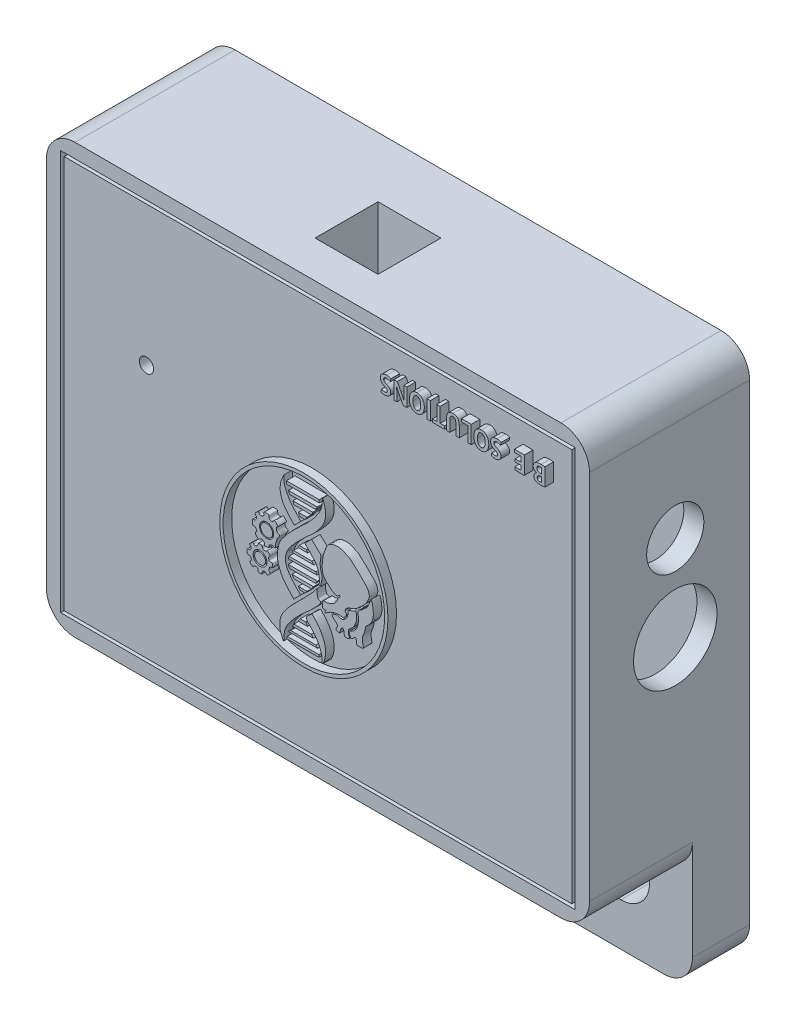
SolidWorks part; units mm, degrees
note: The reader was unsure of these and kept them because the rebuilt part matched: shared geometry of "Sketch12<3>".
ref_plane "Front Plane" through (0, 0, 0) normal (0, 0, 1) x (1, 0, 0)
ref_plane "Top Plane" through (0, 0, 0) normal (0, 1, 0) x (1, 0, 0)
ref_plane "Right Plane" through (0, 0, 0) normal (1, 0, 0) x (0, 0, -1)
sketch "Sketch2" plane through (0, 0, 0) normal (0, 0, 1) x (1, 0, 0)
  line L1 (0, 0) -> (190, 0)
  line L2 (0, 0) -> (0, 150)
  line L3 (0, 150) -> (190, 150)
  line L4 (190, 0) -> (190, 150)
  line L5 (7, 7) -> (183, 7)
  line L6 (7, 7) -> (7, 143)
  line L7 (7, 143) -> (183, 143)
  line L8 (183, 7) -> (183, 143)
  dimension "D1" = 190
  dimension "D2" = 150
  dimension "D3" = 7
  dimension "D4" = 7
  dimension "D5" = 7
  dimension "D6" = 7
extrude "Boss-Extrude1" add sketch "Sketch2" against normal blind 50
sketch "Sketch3" plane through (0, 0, 0) normal (0, 0, 1) x (1, 0, 0)
  line L1 (185, 145) -> (5, 145)
  line L2 (185, 145) -> (185, 5)
  line L3 (185, 5) -> (5, 5)
  line L4 (5, 145) -> (5, 5)
  line L5 (190, 150) -> (0, 150)
  line L6 (190, 150) -> (190, 0)
  line L7 (190, 0) -> (0, 0)
  line L8 (0, 150) -> (0, 0)
  line M9 (183, 7) -> (7, 7)
  line M10 (7, 7) -> (7, 143)
  line M11 (7, 143) -> (183, 143)
  line M12 (183, 143) -> (183, 7)
  dimension "D1" = 5
  dimension "D2" = 5
  dimension "D3" = 5
  dimension "D4" = 5
extrude "Cut-Extrude1" cut sketch "Sketch3" against normal blind 6 contours L1 L4 L3 L2 M12 M9 M10 M11
sketch "Sketch5" plane through (0, 0, -6) normal (0, 0, 1) x (1, 0, 0)
  line L0 (185, 5) -> (5, 5) construction
  line L1 (183.8, 143.8) -> (6.2, 143.8)
  line L2 (183.8, 143.8) -> (183.8, 6.2)
  line L3 (183.8, 6.2) -> (6.2, 6.2)
  line L4 (6.2, 143.8) -> (6.2, 6.2)
  line L5 (5, 145) -> (5, 5) construction
  line L6 (185, 145) -> (5, 145) construction
  line L7 (185, 145) -> (185, 5) construction
  dimension "D1" = 1.2
  dimension "D2" = 1.2
  dimension "D3" = 1.2
  dimension "D4" = 1.2
extrude "Boss-Extrude2" add sketch "Sketch5" along normal up to surface (6 mm away) separate body up to face at (95, 75, 0)
sketch "Sketch6" plane through (0, 0, -50) normal (0, 0, -1) x (-1, 0, 0)
  line L1 (0, 150) -> (-190, 150)
  line L2 (0, 150) -> (0, 0)
  line L3 (0, 0) -> (-190, 0)
  line L4 (-190, 150) -> (-190, 0)
extrude "Boss-Extrude3" add sketch "Sketch6" along normal blind 6
sketch "Sketch8" plane through (0, 0, -56) normal (0, 0, -1) x (-1, 0, 0)
  line L2 (-190, 0) -> (-190, -35)
  line L3 (-190, -35) -> (0, -35)
  line L4 (0, 0) -> (0, -35)
  line L7 (0, 0) -> (-190, 0)
  line L9 (-175, 0) -> (-175, -20)
  line L10 (-175, -20) -> (-15, -20)
  line L11 (-15, 0) -> (-15, -20)
  point P0 (-90, 0)
  point P7 (-135, 0)
  line M15 (-190, 0) -> (0, 0)
  dimension "D1" = 190
  dimension "D2" = 15
  dimension "D3" = 15
  dimension "D4" = 15
  dimension "D5" = 0
  dimension "D6" = 20
extrude "Boss-Extrude5" add sketch "Sketch8" against normal blind 20 contours L11 L10 L9 L2 L3 L4 M15
fillet "Fillet1" radius 10 2 edges at (0, 150, -28) (0, 0, -18)
fillet "Fillet2" radius 10 2 edges at (190, 150, -28) (190, 0, -18)
fillet "Fillet3" radius 10 4 edges at (175, -20, -46) (15, -20, -46) (0, -35, -46) (190, -35, -46)
sketch "Sketch12" plane through (0, 143, 0) normal (0, -1, 0) x (1, 0, 0)
  line L0 (183, -50) -> (183, -6) construction
  line L1 (103, -35) -> (81, -35)
  line L2 (103, -35) -> (103, -13)
  line L3 (103, -13) -> (81, -13)
  line L4 (81, -35) -> (81, -13)
  line L5 (103, -35) -> (81, -13) construction
  line L6 (103, -13) -> (81, -35) construction
  line L7 (183, -50) -> (7, -50) construction
  line L9 (107, -9) -> (77, -9)
  line L10 (107, -9) -> (107, -39)
  line L11 (107, -39) -> (77, -39)
  line L12 (77, -9) -> (77, -39)
  line L13 (107, -9) -> (77, -39) construction
  line L14 (107, -39) -> (77, -9) construction
  point P0 (92, -24)
  point P9 (92, -24)
  dimension "D1" = 22
  dimension "D2" = 22
  dimension "D3" = 80
  dimension "D4" = 15
  dimension "D5" = 4
  dimension "D6" = 4
extrude "Cut-Extrude3" cut sketch "Sketch12" against normal blind 27 contours L2 L1 L4 L3
extrude "Boss-Extrude7" add sketch "Sketch12<3>" along normal blind 25 contours L10 L11 L12 L9
sketch "Sketch12<3>" plane through (0, 143, 0) normal (0, -1, 0) x (1, 0, 0) same geometry as "Sketch12"
sketch "Sketch13" plane through (0, 0, -9) normal (0, 0, 1) x (1, 0, 0)
  line L1 (107, 118) -> (77, 118)
  line L2 (107, 118) -> (107, 115)
  line L3 (107, 115) -> (77, 115)
  line L4 (77, 118) -> (77, 115)
  dimension "D1" = 0
  dimension "D2" = 3
extrude "Boss-Extrude8" add sketch "Sketch13" against normal blind 24
sketch "Sketch14" plane through (190, 0, 0) normal (1, 0, 0) x (0, 0, -1)
  line L0 (56, 75) -> (0, 75) construction
  line L1 (56, 140) -> (56, -25) construction
  line L2 (0, 10) -> (0, 140) construction
  circle A0 centre (30, 75) radius 14.6
  dimension "D2" = 29.2
  dimension "D3" = 30
  dimension "D1" = 70
extrude "Cut-Extrude4" cut sketch "Sketch14" against normal blind 24
sketch "Sketch15" plane through (0, 0, 0) normal (0, 0, 1) x (1, 0, 0)
  line L0 (178, 136.8993) -> (98, 136.8993) construction
  line L2 (185, 145) -> (185, 5) construction
  text T0 "B.E. SOLUTIONS\r\n" font "Adobe Gothic Std B" height in points 20
  dimension "D1" = 7
  dimension "D2" = 80
extrude "Boss-Extrude10" add sketch "Sketch15" along normal blind 3
sketch "Sketch16" plane through (0, 0, 0) normal (0, 0, 1) x (1, 0, 0)
  line L0 (9.3333, -352) -> (-673.3333, -352) construction
  line L1 (92.6849, 54.4735) -> (90.2161, 52.2125)
  line L2 (91.9334, 55.2949) -> (89.5639, 52.9254)
  line L3 (95.7514, 74.0964) -> (93.3973, 71.6991)
  line L4 (93.3973, 71.6991) -> (93.5085, 71.5841)
  line L5 (98.3461, 61.5576) -> (99.1025, 61.5576)
  line L6 (92.0206, 77.667) -> (89.6937, 75.3401)
  line L7 (98.3461, 39.6401) -> (98.3461, 40.4546)
  line L8 (98.3461, 40.4546) -> (87.2348, 40.4546)
  line L9 (87.2348, 40.4546) -> (87.2348, 39.6401)
  line L10 (87.2348, 39.6401) -> (98.3461, 39.6401)
  line L11 (97.8898, 42.126) -> (97.2739, 42.8467)
  line L12 (97.2739, 42.8467) -> (88.4308, 42.8467)
  line L13 (88.4308, 42.8467) -> (87.5876, 42.126)
  line L14 (87.5876, 42.126) -> (97.8898, 42.126)
  line L15 (96.4473, 44.4542) -> (95.7514, 45.3202)
  line L16 (95.7514, 45.3202) -> (89.5639, 45.3202)
  line L17 (89.5639, 45.3202) -> (89.0336, 44.4542)
  line L18 (89.0336, 44.4542) -> (96.4473, 44.4542)
  line L19 (94.3242, 46.9907) -> (91.0841, 46.9907)
  line L20 (91.0841, 46.9907) -> (91.7933, 48.0423)
  line L21 (91.7933, 48.0423) -> (93.6841, 48.0423)
  line L22 (93.6841, 48.0423) -> (94.3242, 46.9907)
  line L23 (94.1769, 57.5409) -> (93.5085, 56.6946)
  line L24 (93.5085, 56.6946) -> (91.7933, 56.6946)
  line L25 (91.7933, 56.6946) -> (91.1131, 57.5409)
  line L26 (91.1131, 57.5409) -> (94.1769, 57.5409)
  line L27 (96.3957, 60.0816) -> (95.719, 59.0603)
  line L28 (95.719, 59.0603) -> (89.6239, 59.0603)
  line L29 (89.6239, 59.0603) -> (88.9199, 60.0816)
  line L30 (88.9199, 60.0816) -> (96.3957, 60.0816)
  line L31 (97.758, 62.4384) -> (97.1874, 61.4488)
  line L32 (97.1874, 61.4488) -> (88.0735, 61.4488)
  line L33 (88.0735, 61.4488) -> (87.5876, 62.4384)
  line L34 (87.5876, 62.4384) -> (97.758, 62.4384)
  line L35 (97.6067, 64.1731) -> (97.2378, 65.0258)
  line L36 (97.2378, 65.0258) -> (87.8826, 65.0258)
  line L37 (87.8826, 65.0258) -> (87.5876, 64.1731)
  line L38 (87.5876, 64.1731) -> (97.6067, 64.1731)
  line L39 (96.5562, 66.7164) -> (95.8785, 67.557)
  line L40 (95.8785, 67.557) -> (89.4203, 67.557)
  line L41 (89.4203, 67.557) -> (88.8793, 66.7164)
  line L42 (88.8793, 66.7164) -> (96.5562, 66.7164)
  line L43 (94.3614, 69.2592) -> (93.9954, 70.0943)
  line L44 (93.9954, 70.0943) -> (91.4569, 70.0943)
  line L45 (91.4569, 70.0943) -> (90.9302, 69.2758)
  line L46 (90.9302, 69.2758) -> (94.3614, 69.2592)
  line L47 (94.1769, 79.9875) -> (91.1131, 79.9875)
  line L48 (91.1131, 79.9875) -> (91.7933, 78.9617)
  line L49 (91.7933, 78.9617) -> (93.5085, 78.9617)
  line L50 (93.5085, 78.9617) -> (94.1769, 79.9875)
  line L51 (96.1948, 82.5266) -> (95.719, 81.5066)
  line L52 (95.719, 81.5066) -> (89.5639, 81.5066)
  line L53 (89.5639, 81.5066) -> (89.2463, 82.5266)
  line L54 (89.2463, 82.5266) -> (96.1948, 82.5266)
  line L55 (97.7527, 84.8946) -> (97.2378, 83.864)
  line L56 (97.2378, 83.864) -> (88.0735, 83.864)
  line L57 (88.0735, 83.864) -> (87.6796, 84.8946)
  line L58 (87.6796, 84.8946) -> (97.7527, 84.8946)
  line L59 (98.4337, 86.4686) -> (98.4337, 87.4496)
  line L60 (98.4337, 87.4496) -> (86.9516, 87.4496)
  line L61 (86.9516, 87.4496) -> (86.9516, 86.4686)
  line L62 (86.9516, 86.4686) -> (98.4337, 86.4686)
  circle A0 centre (93.074, 63.4201) radius 28.2643
  circle A1 centre (93.074, 63.4201) radius 29.417
  circle A2 centre (77.734, 59.328) radius 1.9037
  circle A3 centre (77.734, 59.328) radius 2.4063
  circle A4 centre (80.0465, 68.9893) radius 2.0884
  circle A5 centre (80.0465, 68.9893) radius 2.4688
  spline S0 degree 3 poles (100.0814, 39.1112) (99.4401, 37.9116) (99.4967, 39.8659) (99.3244, 40.7939) (98.8886, 42.3372) (98.2061, 43.7532) (97.388, 45.1029) (96.3568, 46.4662) (95.2159, 47.5835) (94.193, 48.5893) (93.7591, 49.5701) (94.2613, 50.133) (94.692, 50.4928) (95.1699, 50.9134) (95.4839, 51.2743) (96.0754, 51.5285) (96.5483, 50.8523) (97.2086, 50.221) (98.1892, 49.1071) (99.3075, 47.3884) (100.2855, 45.3363) (100.6265, 43.4327) (100.6737, 41.7822) (100.4361, 40.1463) (100.0814, 39.1112) (99.4401, 37.9116) (99.4967, 39.8659) knots -0.123491 -0.065666 -0.01284 0 0.039755 0.085413 0.127589 0.187562 0.242991 0.281899 0.356235 0.397229 0.429388 0.443556 0.466975 0.485881 0.505841 0.514143 0.545002 0.567755 0.609797 0.687896 0.770733 0.831317 0.876509 0.934334 0.98716 1 1.039755 1.085413 1.127589 only from (99.6247, 38.3159) to (99.6247, 38.3159)
  spline S1 degree 3 poles (85.4196, 39.6043) (86.1158, 37.7797) (86.0483, 39.9395) (86.2069, 41.1299) (86.6342, 42.772) (87.4046, 44.1741) (88.1754, 45.184) (88.979, 46.2387) (89.8787, 47.271) (91.165, 48.6525) (92.5075, 49.8902) (93.7687, 51.1266) (94.9955, 52.0558) (96.1288, 53.2053) (97.2902, 54.3109) (98.1886, 55.2936) (98.7359, 56.0378) (98.9055, 56.4995) (99.06, 56.9828) (98.5372, 57.0233) (98.078, 57.1348) (97.8136, 57.9254) (97.5879, 58.6477) (97.8074, 60.4824) (96.5577, 58.5767) (95.6222, 57.7056) (94.4154, 56.2661) (93.2173, 55.2059) (92.278, 54.0644) (91.0849, 53.0399) (90.0988, 51.9677) (88.9174, 50.8452) (87.7961, 49.6019) (86.6602, 48.1509) (85.5886, 46.7046) (85.014, 45.2448) (84.6196, 43.8471) (84.6275, 42.2966) (84.7957, 40.6496) (85.4196, 39.6043) (86.1158, 37.7797) (86.0483, 39.9395) knots -0.080081 -0.042595 -0.023219 0 0.020603 0.051768 0.084205 0.109791 0.141798 0.154959 0.18403 0.218361 0.260543 0.286188 0.317123 0.346418 0.376481 0.406547 0.421867 0.426234 0.435696 0.441637 0.450667 0.461443 0.482878 0.503861 0.523137 0.564277 0.596446 0.62275 0.654702 0.678549 0.710636 0.736113 0.769738 0.804156 0.839403 0.869741 0.891531 0.919919 0.957405 0.976781 1 1.020603 1.051768 1.084205 only from (85.998, 38.4137) to (85.998, 38.4137)
  spline S2 degree 3 poles (91.9334, 55.2949) (91.6406, 55.7586) (90.8902, 56.2469) (90.1919, 57.1207) (89.5579, 57.7611) (88.9438, 58.4408) (88.1526, 59.5625) (87.2316, 60.8609) (86.6476, 62.4983) (86.6273, 63.6811) (86.681, 64.7395) (86.8736, 65.6546) (87.4034, 66.7025) (88.0432, 67.8338) (89.2054, 69.2129) (90.4493, 70.5281) (91.6612, 71.6992) (92.7933, 72.8339) (93.8531, 73.9473) (95.2381, 75.0443) (96.4697, 76.1726) (97.7828, 77.6849) (99.1803, 79.4117) (100.2385, 81.2744) (100.6837, 83.2907) (100.6602, 85.1602) (100.3438, 86.5899) (99.5155, 89.3865) (99.5374, 86.8664) (99.2904, 85.3297) (98.4754, 83.5166) (97.313, 81.956) (96.4612, 80.6548) (95.3391, 79.618) (94.2884, 78.3301) (93.0377, 77.1702) (91.3991, 75.6092) (90.0592, 74.3939) (88.7326, 73.0228) (87.2054, 71.4292) (85.7379, 69.6213) (84.5028, 67.6851) (84.1105, 66.2454) (83.8768, 64.7084) (83.7797, 63.2592) (83.961, 61.4315) (84.5677, 59.5103) (85.656, 57.2186) (87.4999, 55.2161) (88.7313, 53.6243) (89.5639, 52.9254) knots 0 0 0 0 0.019361 0.031665 0.040167 0.05189 0.064656 0.089683 0.10912 0.126258 0.131963 0.147406 0.15948 0.174211 0.194215 0.224289 0.239579 0.255009 0.282159 0.294895 0.318724 0.342314 0.367054 0.39905 0.418045 0.441879 0.462155 0.483751 0.500653 0.518786 0.549837 0.567176 0.589792 0.605427 0.622108 0.649675 0.66685 0.70381 0.714899 0.735691 0.783444 0.798798 0.818064 0.836631 0.854984 0.870281 0.902638 0.927178 0.961174 1 1 1 1
  spline S3 degree 3 poles (98.3461, 61.5576) (98.5654, 62.3743) (98.5292, 63.7294) (98.1478, 65.6942) (97.5798, 67.4088) (96.2837, 68.717) (95.1023, 70.2157) (94.0343, 71.0212) (93.5085, 71.5841) knots 0 0 0 0 0.214269 0.339584 0.513108 0.662845 0.803202 1 1 1 1
  spline S4 degree 3 poles (95.7514, 74.0964) (96.2546, 73.5392) (97.1547, 72.8305) (98.2042, 71.7149) (99.1431, 70.959) (98.8402, 69.5975) (98.7485, 68.5373) (98.8158, 67.3781) (98.9095, 66.4977) (99.2365, 65.5048) (99.5616, 64.5902) (99.3576, 63.2533) (98.9896, 62.3616) (99.1025, 61.5576) knots 0 0 0 0 0.162649 0.23774 0.341133 0.380335 0.523449 0.573125 0.628859 0.712466 0.798393 0.829985 1 1 1 1
  spline S5 degree 3 poles (92.0206, 77.667) (91.4526, 78.3482) (90.3586, 79.4884) (88.9003, 80.9272) (87.8218, 82.5023) (86.9761, 84.1043) (86.2184, 85.9066) (86.0416, 87.145) (86.1166, 89.3695) (85.5949, 87.5063) (85.245, 86.8497) (84.9565, 86.0807) (84.888, 85.1996) (84.7204, 84.2827) (84.8194, 83.2173) (84.983, 82.1999) (85.4346, 80.9357) (86.0476, 79.5475) (87.0629, 78.3162) (88.2367, 76.8716) (89.1835, 75.9566) (89.6937, 75.3401) knots 0 0 0 0 0.094702 0.168963 0.218444 0.297237 0.366362 0.413711 0.461498 0.499868 0.540588 0.559173 0.584765 0.63525 0.657732 0.698753 0.745037 0.800874 0.859797 0.9145 1 1 1 1
  spline S6 degree 3 poles (80.3933, 55.5788) (79.9745, 55.6777) (79.8206, 56.1099) (79.2543, 56.2368) (78.8381, 56.0198) (78.3316, 55.6616) (78.4551, 55.1821) (78.3344, 54.7967) (78.0812, 54.8337) (77.7882, 54.8213) (77.4986, 54.8399) (77.2455, 54.8214) (76.9767, 54.8153) (77.0558, 55.2408) (77.0772, 55.5392) (76.8958, 56.0419) (76.3204, 56.1748) (75.8312, 56.1219) (75.5093, 55.9173) (75.2557, 55.4594) (74.7138, 55.925) (74.4476, 56.2023) (74.1044, 56.6243) (74.5088, 56.8856) (74.6898, 57.2321) (74.6622, 57.7286) (74.504, 58.2676) (73.9162, 58.497) (73.1938, 58.3459) (73.2312, 59.091) (73.1933, 59.5199) (73.2346, 60.13) (73.8612, 60.0956) (74.3797, 60.0738) (74.5514, 60.4641) (74.5436, 60.7921) (74.6354, 61.2234) (74.3276, 61.5223) (74.061, 61.784) (74.1662, 62.0505) (74.3277, 62.1775) (74.5536, 62.3775) (74.7955, 62.6231) (75.0721, 62.8296) (75.4538, 62.8309) (75.5535, 62.3392) (76.0526, 62.3448) (76.4056, 62.4101) (76.7052, 62.6022) (76.8964, 62.8907) (77.0765, 63.1977) (77.0108, 63.6809) (77.5193, 63.6277) (77.8592, 63.6333) (78.1201, 63.6481) (78.4416, 63.6019) (78.4926, 63.2119) (78.5824, 62.7369) (79.1639, 62.4429) (79.8083, 62.4371) (80.2382, 62.9646) (80.6421, 62.5408) (80.9153, 62.3006) (81.2735, 61.8323) (80.6814, 61.3688) (80.7346, 60.7244) (80.8967, 60.1277) (81.3754, 60.0326) (81.7419, 60.152) (82.2129, 59.9066) (82.1102, 59.4238) (82.1176, 59.0556) (82.1206, 58.8458) (82.1248, 58.6435) (81.8668, 58.6099) (81.6315, 58.6492) (81.3167, 58.5659) (81.0403, 58.2563) (80.9488, 57.8024) (80.7467, 57.2131) (81.205, 57.0126) (81.344, 56.5762) (81.1083, 56.1302) (80.7279, 55.8573) (80.3933, 55.5788) (79.9745, 55.6777) (79.8206, 56.1099) knots -0.033495 -0.018596 -0.003552 0 0.017407 0.030087 0.045331 0.05809 0.079752 0.083135 0.090345 0.097375 0.110607 0.114418 0.120656 0.129167 0.142879 0.149923 0.173353 0.185795 0.192526 0.20697 0.220495 0.240654 0.248457 0.26003 0.273012 0.282549 0.303039 0.316727 0.335972 0.350983 0.367549 0.379792 0.394831 0.413365 0.41913 0.429573 0.442763 0.453836 0.465829 0.470619 0.476772 0.483675 0.497016 0.507051 0.513189 0.526631 0.539834 0.550355 0.558824 0.569915 0.580133 0.590432 0.603389 0.612979 0.622526 0.626126 0.639968 0.649299 0.669008 0.688979 0.70445 0.712641 0.732666 0.741443 0.757115 0.783232 0.795829 0.80589 0.821343 0.82899 0.84727 0.856315 0.861823 0.866548 0.871065 0.880951 0.888833 0.89805 0.915171 0.932162 0.940008 0.954283 0.966505 0.981404 0.996448 1 1.017407 1.030087 1.045331 only from (80.1399, 55.6457) to (80.1399, 55.6457)
  spline S7 degree 3 poles (80.8969, 64.4408) (80.8685, 64.0002) (80.6173, 63.9725) (80.3665, 63.9734) (80.0448, 63.9756) (79.7515, 63.9956) (79.5143, 64.0074) (79.2111, 63.9459) (79.2217, 64.4742) (79.2623, 64.971) (78.8472, 65.2788) (78.4745, 65.4389) (78.0597, 65.3958) (77.6518, 65.1854) (77.2689, 64.8256) (76.81, 65.1747) (76.4797, 65.4759) (76.1954, 65.8331) (76.0153, 66.1803) (76.1892, 66.6401) (76.7471, 66.8806) (76.5053, 67.4194) (76.2685, 67.7756) (75.9505, 68.1337) (75.556, 68.1881) (75.1407, 68.1072) (75.1352, 68.5667) (75.1253, 68.9483) (75.1396, 69.3735) (75.1149, 69.6887) (75.1961, 70.119) (75.7814, 69.9111) (76.2339, 70.1959) (76.4327, 70.6263) (76.5364, 71.0437) (76.4891, 71.5368) (76.0407, 71.7006) (76.027, 72.1123) (76.2177, 72.4676) (76.5947, 72.7871) (76.9045, 73.0752) (77.2672, 73.1525) (77.4455, 72.8356) (77.7384, 72.4058) (78.4823, 72.4729) (79.0854, 72.8517) (79.063, 73.4076) (79.0056, 73.7266) (79.0868, 74.0761) (79.4784, 74.1238) (79.8954, 74.1066) (80.3264, 74.1685) (80.7869, 74.0969) (80.9255, 73.7202) (80.8256, 73.3732) (81.0071, 72.9529) (81.3431, 72.5756) (81.9116, 72.5469) (82.3696, 72.8329) (82.5941, 73.2308) (83.0118, 73.2241) (83.3139, 72.9731) (83.5587, 72.6443) (83.8549, 72.4147) (84.1615, 71.9578) (83.3977, 71.7585) (83.5435, 71.0066) (83.562, 70.2891) (84.1424, 70.01) (84.6262, 69.7971) (84.5468, 69.2785) (83.9045, 68.7859) (83.5697, 67.8076) (83.321, 66.7582) (83.0063, 65.9952) (83.2414, 65.0336) (82.6256, 64.9928) (82.3498, 65.5031) (81.635, 65.3362) (80.8221, 65.0837) (80.8969, 64.4408) (80.8685, 64.0002) (80.6173, 63.9725) knots -0.044893 -0.026992 -0.003748 0 0.005057 0.013093 0.021821 0.030655 0.036601 0.041971 0.051372 0.067873 0.084271 0.087384 0.100807 0.115287 0.126061 0.137182 0.154734 0.164445 0.174014 0.184572 0.200704 0.212758 0.223897 0.237643 0.248169 0.257118 0.263566 0.278679 0.291383 0.296618 0.305213 0.320112 0.3333 0.345772 0.357253 0.368678 0.381637 0.388866 0.39876 0.413572 0.428292 0.433314 0.44013 0.454003 0.473911 0.492918 0.504661 0.515564 0.519788 0.53179 0.541049 0.55498 0.567974 0.572701 0.585574 0.595536 0.608404 0.62457 0.636168 0.651698 0.656177 0.668088 0.681597 0.688916 0.699948 0.714888 0.731296 0.753613 0.76825 0.781001 0.79082 0.803789 0.845114 0.870143 0.889995 0.916753 0.921441 0.934419 0.955107 0.973008 0.996252 1 1.005057 1.013093 1.021821 only from (80.8472, 64.0375) to (80.8472, 64.0375)
  spline S8 degree 3 poles (116.1383, 64.8975) (116.4796, 66.7023) (117.1134, 64.9547) (117.2715, 63.9062) (117.3839, 62.4486) (117.3408, 61.046) (116.9235, 59.8185) (116.3745, 58.8721) (115.8116, 58.2033) (115.302, 57.696) (114.6781, 57.3232) (114.6276, 56.6156) (114.4819, 55.9427) (114.334, 55.2574) (114.0369, 54.506) (113.6849, 53.8836) (113.5528, 52.9049) (113.6208, 51.9494) (113.7023, 50.9861) (114.034, 50.2595) (113.4938, 49.9136) (112.8633, 50.0076) (112.262, 49.9525) (111.6113, 49.9335) (111.4179, 50.6565) (111.4303, 51.2073) (111.3198, 52.2723) (110.4405, 51.5943) (110.0474, 51.0675) (109.3109, 51.1856) (109.1975, 51.7343) (108.9931, 52.2048) (108.8083, 52.8403) (109.5152, 53.1288) (110.13, 53.4402) (110.8112, 54.0323) (111.3472, 54.7169) (111.765, 55.5185) (112.0659, 56.4676) (112.1905, 57.6956) (112.1969, 58.9627) (111.8371, 59.9396) (112.1498, 61.0384) (113.2271, 61.3751) (113.8486, 61.9576) (114.29, 62.4209) (114.6561, 62.7485) (115.3053, 63.2167) (115.6254, 64.1071) (116.1383, 64.8975) (116.4796, 66.7023) (117.1134, 64.9547) knots -0.080892 -0.054111 -0.028562 0 0.024895 0.056748 0.091959 0.125613 0.158455 0.184008 0.204368 0.221124 0.236568 0.253185 0.268306 0.287257 0.303344 0.326675 0.33795 0.374208 0.393817 0.412294 0.418778 0.435593 0.456144 0.464998 0.477511 0.500199 0.515069 0.533187 0.55484 0.563866 0.579723 0.58902 0.60348 0.618765 0.634979 0.655747 0.682344 0.697577 0.720765 0.753702 0.78645 0.811389 0.826844 0.863021 0.883639 0.888601 0.909185 0.919108 0.945889 0.971438 1 1.024895 1.056748 1.091959 only from (116.5429, 66.1248) to (116.5429, 66.1248)
  spline S9 degree 3 poles (110.7889, 60.0361) (111.4235, 60.0768) (111.3711, 59.1444) (111.5945, 58.2962) (111.4569, 57.1485) (111.0288, 55.9562) (110.4088, 54.7702) (109.4391, 53.8929) (108.5293, 53.1737) (108.6338, 52.3641) (108.6881, 51.7893) (108.9315, 51.3234) (109.2766, 50.6355) (108.4226, 50.4319) (107.9518, 50.4192) (107.4394, 50.266) (107.2105, 50.7354) (107.1366, 51.3487) (107.095, 51.9761) (106.8193, 52.7321) (106.0259, 52.4336) (105.9341, 51.6778) (105.7271, 51.0923) (105.6704, 50.5194) (105.1343, 50.6449) (104.7788, 50.7573) (104.3719, 50.8656) (104.3188, 51.4642) (104.7409, 51.9079) (104.8552, 52.716) (104.3001, 53.265) (103.7153, 53.6679) (103.2676, 54.1863) (102.8339, 54.6978) (103.0612, 55.1608) (103.4543, 55.2907) (103.9409, 55.3724) (104.4851, 55.6327) (105.1171, 55.6627) (105.5314, 55.2242) (106.0599, 55.2458) (106.4339, 55.211) (106.9175, 55.3745) (107.3867, 55.6984) (107.8455, 56.2216) (108.2369, 56.6279) (108.3698, 57.2243) (108.4949, 57.8031) (108.5188, 58.359) (108.3518, 58.9381) (109.052, 59.2268) (109.7024, 59.3983) (110.3868, 59.6619) (110.7889, 60.0361) (111.4235, 60.0768) (111.3711, 59.1444) knots -0.048615 -0.025403 -0.010482 0 0.020654 0.050289 0.085331 0.117015 0.162834 0.199294 0.235319 0.252053 0.267723 0.285279 0.301154 0.321187 0.341074 0.349771 0.362311 0.378057 0.406126 0.421939 0.433835 0.466281 0.480473 0.492579 0.507195 0.516567 0.52876 0.538836 0.562157 0.580812 0.603621 0.625216 0.64355 0.665638 0.675656 0.682757 0.700984 0.719098 0.735813 0.752193 0.767436 0.78011 0.784896 0.811922 0.828696 0.846551 0.859968 0.881418 0.898354 0.910046 0.927903 0.951385 0.974597 0.989518 1 1.020654 1.050289 1.085331 only from (111.2317, 60.0105) to (111.2317, 60.0105)
  spline S10 degree 3 poles (107.4304, 57.8954) (108.1413, 57.9063) (108.0244, 57.2223) (107.6686, 56.8172) (107.4006, 56.2995) (106.9641, 55.8411) (106.2765, 55.9272) (105.4285, 56.1618) (104.3805, 55.9424) (103.1899, 55.7006) (102.0131, 55.1864) (101.2144, 54.5989) (100.7544, 54.2016) (100.501, 54.2083) (100.3943, 54.5204) (100.5896, 54.7209) (100.8921, 55.1381) (100.2099, 55.0021) (99.9108, 55.1196) (99.3917, 55.3043) (99.6805, 56.0462) (99.641, 56.6526) (99.5508, 57.1546) (99.8369, 57.6109) (100.3796, 57.6558) (100.9624, 57.4754) (101.5228, 57.7383) (102.1677, 57.7937) (102.7161, 58.1739) (103.2676, 58.408) (103.8531, 58.6392) (104.0479, 59.2541) (104.6438, 59.7695) (104.896, 60.6668) (105.3044, 61.2921) (105.905, 61.7911) (105.4304, 62.2273) (105.1188, 61.5603) (104.4232, 61.3621) (103.7216, 61.7297) (102.9054, 62.0329) (102.2822, 62.6338) (101.4624, 63.3197) (100.6946, 64.085) (99.7448, 65.3007) (99.4526, 66.9399) (99.4725, 68.6136) (99.6109, 69.9808) (99.811, 71.2566) (100.2964, 72.602) (100.7274, 74.0614) (101.7079, 75.7251) (103.5962, 76.4843) (105.8745, 76.5529) (107.6691, 75.7014) (109.3302, 75.0503) (110.3475, 73.8603) (111.6395, 72.9361) (112.822, 71.5288) (114.0456, 70.395) (115.4511, 69.0076) (116.3009, 67.0424) (115.4302, 65.3697) (114.6287, 63.7082) (113.0014, 62.3718) (111.4745, 60.9179) (109.9529, 60.2422) (108.5825, 59.7501) (107.6251, 59.0916) (107.4304, 57.8954) (108.1413, 57.9063) (108.0244, 57.2223) knots -0.034028 -0.01535 -0.004263 0 0.008033 0.015493 0.02437 0.032249 0.039793 0.051392 0.069467 0.083128 0.102592 0.122453 0.124681 0.127819 0.131197 0.135649 0.139828 0.146651 0.152789 0.15597 0.167463 0.176191 0.183736 0.187317 0.197498 0.203088 0.212706 0.221773 0.229904 0.239864 0.247509 0.254481 0.26518 0.279808 0.291022 0.299934 0.303082 0.312184 0.320279 0.33218 0.34352 0.356844 0.367712 0.388454 0.402179 0.431619 0.455272 0.472645 0.489091 0.50921 0.532314 0.553023 0.58763 0.611504 0.647047 0.669461 0.684794 0.711572 0.73566 0.76146 0.781105 0.819603 0.838335 0.857641 0.896748 0.924483 0.945423 0.965972 0.98465 0.995737 1 1.008033 1.015493 1.02437 only from (107.973, 57.8527) to (107.973, 57.8527)
  spline S11 degree 3 poles (104.0518, 61.0213) (104.4161, 60.4173) (104.0094, 59.8054) (103.236, 59.0862) (101.8482, 58.5518) (100.3849, 58.1089) (99.3519, 57.7512) (98.4278, 57.6841) (98.3557, 58.3621) (98.1678, 59.0977) (98.9645, 59.0232) (99.4801, 59.1719) (99.9036, 59.2779) (100.2461, 59.4145) (100.2231, 59.8827) (99.6359, 59.678) (99.192, 59.7513) (98.712, 59.7594) (98.3412, 59.6968) (97.9706, 59.9618) (98.0424, 60.4062) (98.0448, 61.0478) (98.5653, 60.8641) (98.9694, 60.9945) (99.1618, 60.5144) (99.5183, 60.6373) (99.9304, 60.5422) (99.7448, 60.9555) (99.5712, 61.3016) (99.4665, 61.8826) (99.5667, 62.5294) (99.6542, 63.1811) (99.5863, 63.8112) (100.1631, 64.2151) (100.5058, 63.4978) (100.6855, 62.9944) (101.069, 62.4723) (101.585, 62.2307) (102.1605, 61.8181) (102.7609, 61.5349) (103.3771, 61.0133) (104.0518, 61.0213) (104.4161, 60.4173) (104.0094, 59.8054) knots -0.0705 -0.046296 -0.009718 0 0.034324 0.063592 0.13428 0.211136 0.247947 0.278605 0.298795 0.325106 0.348774 0.373211 0.395423 0.402603 0.416004 0.432578 0.459554 0.476475 0.490496 0.504819 0.523736 0.544845 0.56348 0.575969 0.591656 0.609798 0.6182 0.631304 0.645057 0.673697 0.698066 0.725718 0.755824 0.76849 0.7968 0.823671 0.842612 0.872749 0.892429 0.9295 0.953704 0.990282 1 1.034324 1.063592 1.13428 only from (104.2833, 60.5998) to (104.2833, 60.5998)
extrude "Boss-Extrude11" add sketch "Sketch16" along normal blind 3
sketch "Sketch17" plane through (0, 0, 0) normal (0, 0, 1) x (1, 0, 0)
  line L0 (185, 145) -> (185, 5) construction
  line L1 (185, 145) -> (5, 145) construction
  circle A0 centre (35, 95) radius 2.5
  dimension "D1" = 150
  dimension "D2" = 5
  dimension "D3" = 50
extrude "Cut-Extrude5" cut sketch "Sketch17" against normal blind 33
sketch "Sketch18" plane through (190, 0, 0) normal (1, 0, 0) x (0, 0, -1)
  line L0 (30, 75) -> (30, 105) construction
  line L1 (56, 140) -> (0, 140) construction
  circle A0 centre (30, 105) radius 10
  dimension "D1" = 20
  dimension "D2" = 35
extrude "Cut-Extrude6" cut sketch "Sketch18" against normal blind 10
